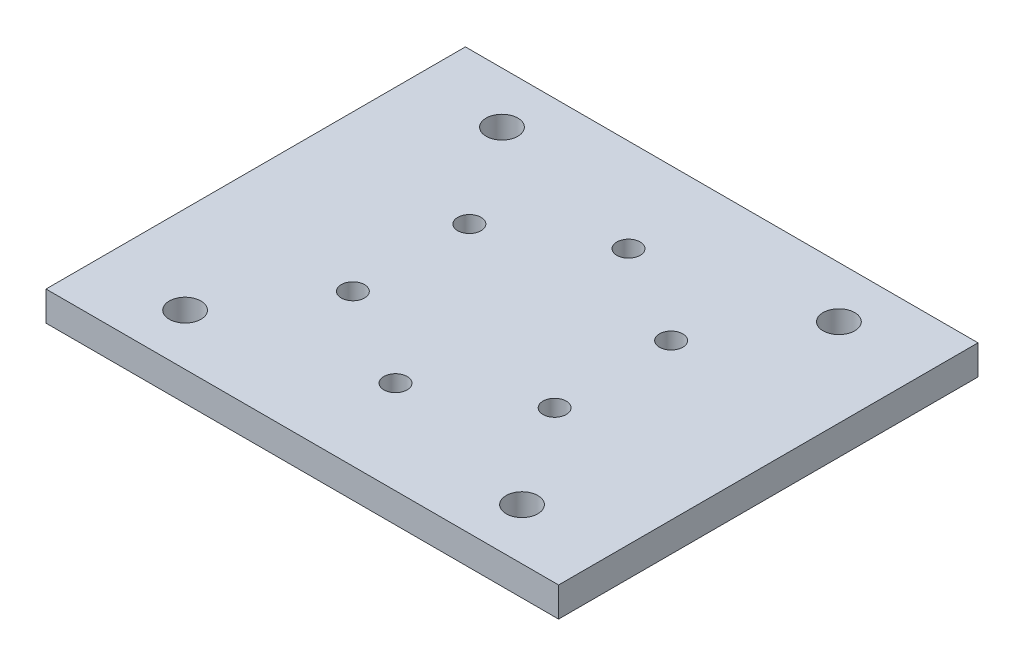
SolidWorks part; units mm, degrees
ref_plane "Front Plane" through (0, 0, 0) normal (0, 0, 1) x (1, 0, 0)
ref_plane "Top Plane" through (0, 0, 0) normal (0, 1, 0) x (1, 0, 0)
ref_plane "Right Plane" through (0, 0, 0) normal (1, 0, 0) x (0, 0, -1)
sketch "Sketch2" plane through (0, 0, 0) normal (0, 1, 0) x (1, 0, 0)
  line L0 (0, 0) -> (0, 90)
  line L1 (0, 90) -> (110, 90)
  line L2 (110, 90) -> (110, 0)
  line L3 (110, 0) -> (0, 0)
  dimension "D1" = 110
  dimension "D2" = 90
extrude "Boss-Extrude1" add sketch "Sketch2" along normal blind 6.35
sketch "Sketch3" plane through (0, 6.35, 0) normal (0, 1, 0) x (1, 0, 0)
  line L1 (110, 90) -> (0, 90) construction
  line L2 (0, 0) -> (110, 0) construction
  line L4 (55, 90) -> (55, 0) construction
  line L5 (0, 45) -> (55, 45) construction
  line L6 (55, 45) -> (110, 45) construction
  line L7 (0, 90) -> (0, 0) construction
  circle A0 centre (18.85, 79) radius 3.4
  circle A1 centre (18.85, 11) radius 3.4
  circle A2 centre (91.15, 11) radius 3.4
  circle A3 centre (91.15, 79) radius 3.4
  dimension "D4" = 6.8
  dimension "D3" = 11
  dimension "D2" = 18.85
extrude "Mounting Holes" cut sketch "Sketch3" against normal through all
sketch "Sketch4" plane through (0, 6.35, 0) normal (0, 1, 0) x (1, 0, 0)
  line L0 (18.85, 79) -> (91.15, 11) construction
  circle A0 centre (55, 45) radius 25 construction
  circle A1 centre (55, 70) radius 2.5
  circle A2 centre (76.6506, 57.5) radius 2.5
  circle A3 centre (76.6506, 32.5) radius 2.5
  circle A4 centre (55, 20) radius 2.5
  circle A5 centre (33.3494, 32.5) radius 2.5
  circle A6 centre (33.3494, 57.5) radius 2.5
  point P9 (0, 0)
  point P10 (0, 0)
  point P20 (55, 45)
  dimension "D1" = 50
  dimension "D2" = 5
  dimension "D3" = 6
extrude "Cut-Extrude1" cut sketch "Sketch4" against normal through all
equation "\"L1L\"=500"
equation "\"L1Thick\"=6.35"
equation "\"Harm-Drive-Outer\"=74.5"
equation "\"L1-Spacing\"=100"
equation "\"L-Bracket-HoleToWall\"=12.5"
equation "\"D3@Sketch3\"=\"L-Bracket-HoleToSide\""
equation "\"L-Bracket-HoleToSide\"=11"
equation "\"Bracket-Hole-D\"=6.8"
equation "\"D4@Sketch3\"=\"Bracket-Hole-D\""
equation "\"L1-Spacing\"=115.65"
equation "\"D2@Sketch3\"=\"L-Bracket-HoleToWall\"+\"L1Thick\""
